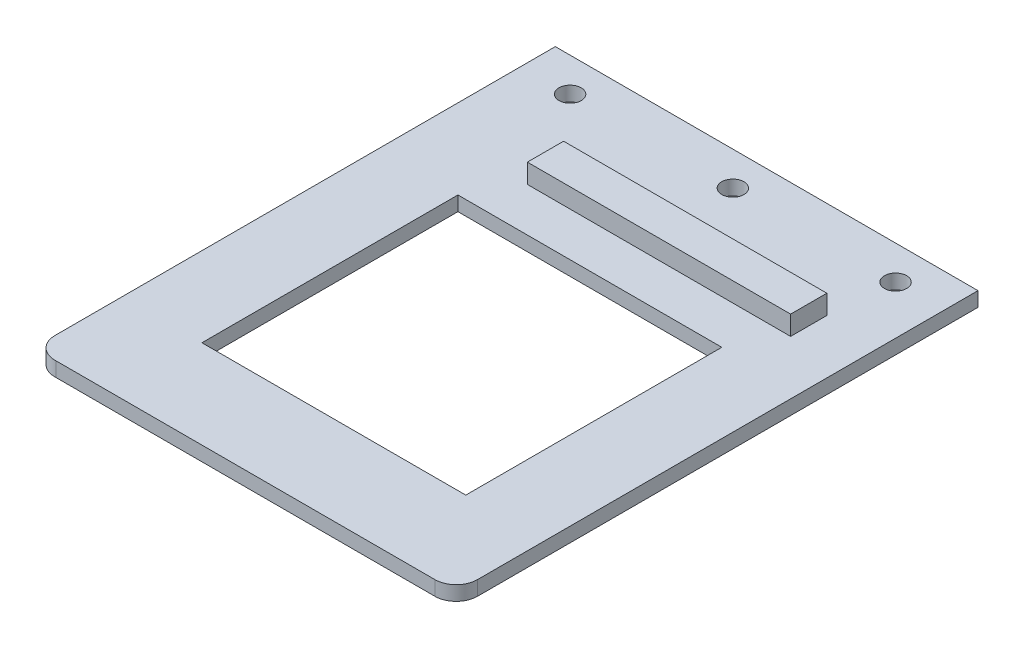
SolidWorks part; units mm, degrees
ref_plane "Front Plane" through (0, 0, 0) normal (0, 0, 1) x (1, 0, 0)
ref_plane "Top Plane" through (0, 0, 0) normal (0, 1, 0) x (1, 0, 0)
ref_plane "Right Plane" through (0, 0, 0) normal (1, 0, 0) x (0, 0, -1)
sketch "Sketch1" plane through (0, 0, 0) normal (0, 1, 0) x (1, 0, 0)
  line L9 (-22.8759, -25.5118) -> (16.3453, -25.5118)
  line L10 (-16.9379, -16.3429) -> (10.3671, -16.3429)
  line L11 (10.3671, -16.3429) -> (10.3671, 10.1491)
  line L12 (10.3671, 10.1491) -> (-16.9379, 10.1491)
  line L13 (-16.9379, 10.1491) -> (-16.9379, -16.3429)
  line L16 (-14.2871, 14.6854) -> (12.9539, 14.6854)
  line L17 (12.9539, 14.6854) -> (12.9539, 18.4324)
  line L18 (12.9539, 18.4324) -> (-14.2871, 18.4324)
  line L19 (-14.2871, 18.4324) -> (-14.2871, 14.6854)
  line L22 (-25.1937, -23.3118) -> (-25.1937, 28.4832)
  line L23 (18.5453, 28.4832) -> (18.5453, -23.3118)
  line L24 (-25.1937, 28.4832) -> (18.5453, 28.4832)
  circle A0 centre (-20.1649, 24.9832) radius 1.15
  circle A1 centre (-3.3249, 24.9832) radius 1.15
  circle A2 centre (13.5151, 24.9832) radius 1.15
  arc A3 (-25.1937, -23.3118) -> (-22.8759, -25.5118) centre (-22.9907, -23.3118) ccw
  arc A4 (18.5453, -23.3118) -> (16.3453, -25.5118) centre (16.3453, -23.3118) cw
extrude "Boss-Extrude1" add sketch "Sketch1" along normal blind 1.5
sketch "Sketch2" plane through (0, 1.5, 0) normal (0, 1, 0) x (1, 0, 0)
  line L0 (-14.2871, 18.4324) -> (12.9539, 18.4324)
  line L1 (12.9539, 18.4324) -> (12.9539, 14.6854)
  line L2 (12.9539, 14.6854) -> (-14.2871, 14.6854)
  line L3 (-14.2871, 14.6854) -> (-14.2871, 18.4324)
  line L4 (18.5453, 28.4832) -> (-25.1937, 28.4832)
  line L5 (-25.1937, 28.4832) -> (-25.1937, -23.3118)
  line L6 (-22.8759, -25.5118) -> (16.3453, -25.5118)
  line L7 (18.5453, -23.3118) -> (18.5453, 28.4832)
  line L8 (18.5453, 28.4832) -> (-25.1937, 28.4832)
  line L9 (-25.1937, 28.4832) -> (-25.1937, -23.3118)
  line L10 (-22.8759, -25.5118) -> (16.3453, -25.5118)
  line L11 (18.5453, -23.3118) -> (18.5453, 28.4832)
  arc A2 (-25.1937, -23.3118) -> (-22.8759, -25.5118) centre (-22.9907, -23.3118) ccw
  arc A3 (16.3453, -25.5118) -> (18.5453, -23.3118) centre (16.3453, -23.3118) ccw
  arc A4 (-25.1937, -23.3118) -> (-22.8759, -25.5118) centre (-22.9907, -23.3118) ccw
  arc A5 (16.3453, -25.5118) -> (18.5453, -23.3118) centre (16.3453, -23.3118) ccw
  dimension "D1" = 0
extrude "Boss-Extrude2" add sketch "Sketch2" along normal blind 2 separate body contours L3 L0 L1 L2
sketch "Sketch3" plane through (0, 1.5, 0) normal (0, -1, 0) x (1, 0, 0)
  line L4 (12.9539, -14.6854) -> (-14.2871, -14.6854)
  line L5 (-14.2871, -14.6854) -> (-14.2871, -18.4324)
  line L6 (-14.2871, -18.4324) -> (12.9539, -18.4324)
  line L7 (12.9539, -18.4324) -> (12.9539, -14.6854)
  line L8 (12.9539, -14.6854) -> (-14.2871, -14.6854)
  line L9 (-14.2871, -14.6854) -> (-14.2871, -18.4324)
  line L10 (-14.2871, -18.4324) -> (12.9539, -18.4324)
  line L11 (12.9539, -18.4324) -> (12.9539, -14.6854)
  dimension "D1" = 0
extrude "Boss-Extrude3" add sketch "Sketch3" along normal up to surface (1.5 mm away) up to face at (-3.3249, 0, -23.8332)
